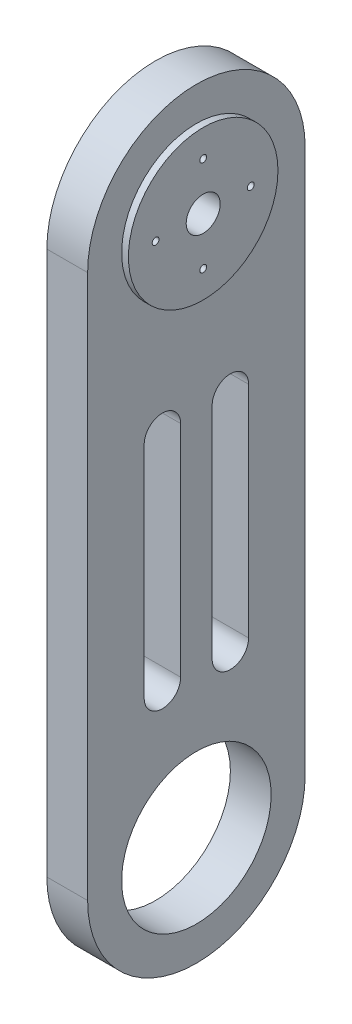
SolidWorks part; units mm, degrees
ref_plane "Front Plane" through (0, 0, 0) normal (0, 0, 1) x (1, 0, 0)
ref_plane "Top Plane" through (0, 0, 0) normal (0, 1, 0) x (1, 0, 0)
ref_plane "Right Plane" through (0, 0, 0) normal (1, 0, 0) x (0, 0, -1)
sketch "Sketch1" plane through (0, 0, 0) normal (1, 0, 0) x (0, 0, -1)
  line L0 (61.13, 0) -> (-61.13, 0) construction
  line L1 (0, 80) -> (0, -80) construction
  line L4 (-16, 0) -> (-16, -80)
  line L5 (16, 0) -> (16, -80)
  circle A0 centre (0, 0) radius 11
  arc A1 (16, 0) -> (-16, 0) centre (0, 0) ccw
  circle A2 centre (0, -80) radius 11
  arc A3 (-16, -80) -> (16, -80) centre (0, -80) ccw
  point P7 (0, 0)
  point P10 (0, 0)
  dimension "D1" = 22
  dimension "D2" = 32
  dimension "D3" = 22
  dimension "D4" = 32
  dimension "D5" = 80
extrude "Boss-Extrude1" add sketch "Sketch1" along normal blind 3 and the other way blind 3
extrude "Boss-Extrude2" add sketch "Sketch1<2>" along normal blind 4 and the other way blind 2 contours A0 region at (0, 0, 0)
sketch "Sketch1<2>" plane through (0, 0, 0) normal (1, 0, 0) x (0, 0, -1) same geometry as "Sketch1"
sketch "Sketch2" plane through (3, 0, 0) normal (1, 0, 0) x (0, 0, -1)
  line L0 (0, 0) -> (0, -96) construction
  line L1 (-5, -26.0714) -> (-5, -58.3822) construction
  line L2 (-2.3176, -26.0714) -> (-2.3176, -58.3822)
  line L3 (-7.6824, -26.0714) -> (-7.6824, -58.3822)
  line L4 (5, -26.0714) -> (5, -58.3822) construction
  line L5 (2.3176, -26.0714) -> (2.3176, -58.3822)
  line L6 (7.6824, -26.0714) -> (7.6824, -58.3822)
  arc A0 (-16, -80) -> (16, -80) centre (0, -80) ccw construction
  arc A1 (-2.3176, -26.0714) -> (-7.6824, -26.0714) centre (-5, -26.0714) ccw
  arc A2 (-7.6824, -58.3822) -> (-2.3176, -58.3822) centre (-5, -58.3822) ccw
  arc A3 (2.3176, -26.0714) -> (7.6824, -26.0714) centre (5, -26.0714) cw
  arc A4 (7.6824, -58.3822) -> (2.3176, -58.3822) centre (5, -58.3822) cw
  point P8 (-5, -42.2268)
  point P15 (5, -42.2268)
  dimension "D1" = 10
extrude "Cut-Extrude1" cut sketch "Sketch2" against normal up to surface (6 mm away) up to face at (-3, -80, -11)
sketch "Sketch3" plane through (-2, 0, 0) normal (-1, 0, 0) x (0, 0, 1)
  line L0 (0, 7) -> (0, -7) construction
  line L1 (7, 0) -> (-7, 0) construction
  circle A0 centre (0, 0) radius 2.5
  circle A1 centre (0, 7) radius 0.5
  circle A2 centre (-7, 0) radius 0.5
  circle A3 centre (7, 0) radius 0.5
  circle A4 centre (0, -7) radius 0.5
  point P6 (0, 0)
  point P10 (0, 0)
  dimension "D1" = 5
  dimension "D3" = 1
  dimension "D2" = 14
  dimension "D4" = 14
extrude "Cut-Extrude2" cut sketch "Sketch3" against normal up to surface (6 mm away) up to face at (4, 0, -11)
